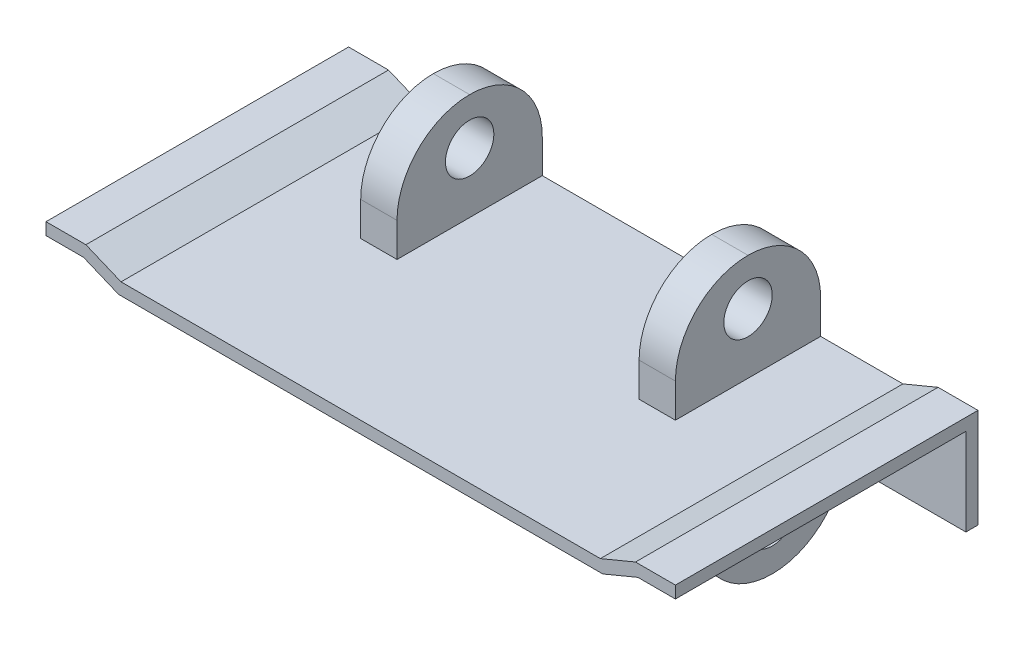
SolidWorks part; units mm, degrees
ref_plane "Front Plane" through (0, 0, 0) normal (0, 0, 1) x (1, 0, 0)
ref_plane "Top Plane" through (0, 0, 0) normal (0, 1, 0) x (1, 0, 0)
ref_plane "Right Plane" through (0, 0, 0) normal (1, 0, 0) x (0, 0, -1)
sketch "Sketch2" plane through (0, 0, 0) normal (0, 0, 1) x (1, 0, 0)
  line L0 (-5, 6) -> (-10, 6)
  line L1 (-5, 6) -> (5, 6) construction
  line L2 (-5, 6) -> (-5, -6) construction
  line L3 (-5, -6) -> (5, -6) construction
  line L4 (5, 6) -> (5, -6) construction
  line L5 (-5, 6) -> (5, -6) construction
  line L6 (-5, -6) -> (5, 6) construction
  line L7 (-10, 6) -> (-10, -6)
  line L8 (-10, -6) -> (-5, -6)
  line L9 (-5, -6) -> (-5, 6)
  line L10 (0, 6) -> (0, -6) construction
  line L11 (10, -6) -> (5, -6)
  line L12 (10, 6) -> (10, -6)
  line L13 (5, 6) -> (10, 6)
  line L14 (5, -6) -> (5, 6)
  point P0 (0, 0)
  point P11 (0, 0)
  point P16 (0, 6)
  dimension "D1" = 12
  dimension "D2" = 10
  dimension "D3" = 5
extrude "Boss-Extrude1" add sketch "Sketch2" along normal blind 12
sketch "Sketch4" plane through (0, 0, 0) normal (0, 0, 1) x (1, 0, 0)
  line L0 (0, 0) -> (0, 50000) construction
  line L1 (-6.1796, 6) -> (49993.8204, 6) construction
  line L2 (-10, 6) -> (-20, 6)
  line L3 (10, 6) -> (20, 6)
  line L4 (-20, 6) -> (-22.9016, 7.2064)
  line L5 (-22.9016, 7.2064) -> (-26, 7.2064)
  line L6 (-10, 7) -> (-19.8004, 7)
  line L7 (-19.8004, 7) -> (-22.702, 8.2064)
  line L8 (-22.702, 8.2064) -> (-26, 8.2064)
  line L9 (-26, 8.2064) -> (-26, 7.2064)
  line L10 (-10, 6) -> (10, 6)
  line L11 (-10, 7) -> (10, 7)
  line L12 (10, 7) -> (19.8004, 7)
  line L13 (19.8004, 7) -> (22.702, 8.2064)
  line L14 (20, 6) -> (22.9016, 7.2064)
  line L15 (22.9016, 7.2064) -> (26, 7.2064)
  line L16 (26, 8.2064) -> (26, 7.2064)
  line L17 (22.702, 8.2064) -> (26, 8.2064)
  point P19 (0, 6)
  point P20 (0, 7)
  dimension "D1" = 10
  dimension "D3" = 6
  dimension "D2" = 1
extrude "Boss-Extrude3" add sketch "Sketch4" along normal blind 25
sketch "Sketch9" plane through (0, 0, 12) normal (0, 0, 1) x (1, 0, 0)
  line L0 (-10, -6) -> (-5, -6) construction
  line L1 (-5, 6) -> (-7.5, 6)
  line L2 (-5, 6) -> (-5, -6)
  line L3 (-5, -6) -> (-7.5, -6)
  line L4 (-7.5, 6) -> (-7.5, -6)
  line L5 (0, 7.972) -> (0, -7.972) construction
  line L6 (5, -6) -> (7.5, -6)
  line L7 (7.5, 6) -> (7.5, -6)
  line L8 (5, 6) -> (7.5, 6)
  line L9 (5, 6) -> (5, -6)
  point P11 (0, 0)
  dimension "D1" = 2.5
extrude "Cut-Extrude1" [suppressed] cut sketch "Sketch9" against normal blind 10
sketch "Sketch5" plane through (0, 0, 0) normal (0, 0, 1) x (1, 0, 0)
  line L0 (-10, 4.6) -> (-10, 50004.6) construction
  line L1 (0, 0) -> (0, 50000) construction
  line L2 (-10, 7) -> (-10, 15.8)
  line L3 (19.8004, 7) -> (-19.8004, 7) construction
  line L4 (-10, 15.8) -> (-13, 15.8)
  line L5 (-13, 15.8) -> (-13, 7)
  line L6 (-13, 7) -> (-10, 7)
  line L7 (13, 7) -> (10, 7)
  line L8 (13, 15.8) -> (13, 7)
  line L9 (10, 15.8) -> (13, 15.8)
  line L10 (10, 7) -> (10, 15.8)
  dimension "D1" = 3
  dimension "D2" = 8.8
extrude "Boss-Extrude4" add sketch "Sketch5" along normal blind 12
sketch "Sketch7" plane through (0, 0, 0) normal (0, 0, 1) x (1, 0, 0)
  line L0 (-13, 5.6) -> (-13, -49994.4) construction
  line L1 (-19.8004, 5.6) -> (-19.8004, -49994.4) construction
  line L2 (-10.0004, -6) -> (49989.9996, -6) construction
  line L3 (-15.0004, 6) -> (-50015.0004, 6) construction
  line L4 (-15, 6) -> (-15, -6)
  line L5 (-15, -6) -> (-13, -6)
  line L6 (-13, -6) -> (-13, 6)
  line L7 (-13, 6) -> (-15, 6)
  line L8 (0, 0) -> (0, -50000) construction
  line L13 (0, -11.99) -> (0, 11.99) construction
  line L14 (13, -6) -> (13, 6)
  line L15 (15, -6) -> (13, -6)
  line L16 (15, 6) -> (15, -6)
  line L17 (13, 6) -> (15, 6)
  dimension "D1" = 2
extrude "Boss-Extrude5" add sketch "Sketch7" along normal blind 12
sketch "Sketch15" plane through (0, -6, 0) normal (0, -1, 0) x (1, 0, 0)
  line L16 (-10, 12) -> (-9.8, 12)
  line L17 (-10, 12) -> (-5, 12) construction
  line L18 (-10, 12) -> (-10, 0) construction
  line L19 (-9.8, 12) -> (-9.8, 0)
  line L20 (-10, 0) -> (-5, 0) construction
  line L21 (-9.8, 0) -> (-10, 0)
  line L22 (-10, 0) -> (-10, 12)
  line L23 (0, -11.99) -> (0, 11.99) construction
  line L24 (9.8, 0) -> (10, 0)
  line L25 (9.8, 12) -> (9.8, 0)
  line L26 (10, 12) -> (9.8, 12)
  line L27 (10, 0) -> (10, 12)
  line L28 (-13, 12) -> (-13.2, 12)
  line L29 (-15, 12) -> (-13, 12) construction
  line L30 (-13.2, 12) -> (-13.2, 0)
  line L31 (-15, 0) -> (-13, 0) construction
  line L32 (-13.2, 0) -> (-13, 0)
  line L33 (-13, 0) -> (-13, 12)
  line L34 (13.2, 0) -> (13, 0)
  line L35 (13.2, 12) -> (13.2, 0)
  line L36 (13, 12) -> (13.2, 12)
  line L37 (13, 0) -> (13, 12)
  dimension "D1" = 0.2
  dimension "D2" = 0.2
extrude "Cut-Extrude2" cut sketch "Sketch15" against normal up to surface (12 mm away) up to face at (0, 6, 7.3)
sketch "Sketch16" plane through (0, -6, 0) normal (0, -1, 0) x (1, 0, 0)
  line L0 (-5, 12) -> (-5.15, 12)
  line L1 (-9.8, 12) -> (-5, 12) construction
  line L2 (-5.15, 12) -> (-5.15, 0)
  line L3 (-9.8, 0) -> (-5, 0) construction
  line L4 (-5.15, 0) -> (-5, 0)
  line L5 (-5, 0) -> (-5, 12)
  line L6 (0, -11.99) -> (0, 11.99) construction
  line L7 (5.15, 0) -> (5, 0)
  line L8 (5.15, 12) -> (5.15, 0)
  line L9 (5, 12) -> (5.15, 12)
  line L10 (5, 0) -> (5, 12)
  dimension "D1" = 0.15
extrude "Cut-Extrude3" cut sketch "Sketch16" against normal up to surface (12 mm away) up to face at (0, 6, 7.3)
fillet "Fillet1" radius 6 8 edges at (7.475, -6, 0) (7.475, -6, 12) (-7.475, -6, 0) (-7.475, -6, 12) (-14.1, -6, 0) (-14.1, -6, 12) (14.1, -6, 0) (14.1, -6, 12)
hole_wizard "Ø4.0mm Dowel Hole2" positions "Sketch10" profile "Sketch11" hole size "Ø4.0" standard "ANSI Metric" end condition through all
sketch "Sketch10" plane through (15, 0, 0) normal (1, 0, 0) x (0, 0, -1)
  line L7 (-25, 6) -> (0, 6) construction
  line L9 (-12, 0) -> (-12, 6) construction
  point P0 (-6, -2)
  dimension "D1" = 6
  dimension "D2" = 8
sketch "Sketch11" plane through (15, -2, 6) normal (0, 1, 0) x (0, 0, -1)
  line L0 (0, 0) -> (0, 41)
  line L1 (0, 41) -> (2, 41)
  line L2 (2, 41) -> (2, 0)
  line L5 (2, 0) -> (0, 0)
  line L11 (0, -6.35) -> (0, 107.95) construction
  dimension "Thru Hole Dia." = 4
  dimension "Thru Hole Depth" = 41
fillet "Fillet2" radius 6 4 edges at (-11.5, 15.8, 0) (-11.5, 15.8, 12) (11.5, 15.8, 0) (11.5, 15.8, 12)
hole_wizard "Ø4.0mm Dowel Hole1" positions "Sketch12" profile "Sketch13" hole size "Ø4.0" standard "ANSI Metric"
sketch "Sketch12" plane through (13, 0, 0) normal (1, 0, 0) x (0, 0, -1)
  circle A0 centre (-6, -0.575) radius 2 construction
  circle A1 centre (-6, -0.575) radius 2 construction
  arc A7 (0, 9.8) -> (-6, 15.8) centre (-6, 9.8) ccw construction
  point P10 (-6, 11.975)
  dimension "D1" = 3.825
sketch "Sketch13" plane through (13, 11.975, 6) normal (0, 1, 0) x (0, 0, -1)
  line L0 (0, 0) -> (0, 27.2017)
  line L1 (0, 27.2017) -> (2, 26)
  line L2 (2, 26) -> (2, 0)
  line L5 (2, 0) -> (0, 0)
  line L10 (0, 27.2017) -> (-2, 26) construction
  line L11 (0, -6.35) -> (0, 107.95) construction
  dimension "Hole Dia." = 4
  dimension "Hole Depth" = 26
  dimension "Drill Angle" = 118
sketch "Sketch14" plane through (0, 0, 0) normal (0, 0, 1) x (1, 0, 0)
  line L4 (0, 14.6739) -> (0, -14.6739) construction
  line L5 (-26, 7.2064) -> (-22.9016, 7.2064)
  line L6 (-26, 6) -> (-26, 7.2064)
  line L7 (-20, 6) -> (-26, 6)
  line L8 (-22.9016, 7.2064) -> (-20, 6)
  line L13 (-15, 6) -> (-20, 6)
  line L14 (-26, 0) -> (-26, 6)
  line L15 (-15, 0) -> (-26, 0)
  line L18 (-15, 6) -> (-15, 0)
  line L21 (15, 6) -> (15, 0)
  line L22 (15, 0) -> (26, 0)
  line L23 (26, 0) -> (26, 6)
  line L24 (15, 6) -> (20, 6)
  line L25 (22.9016, 7.2064) -> (20, 6)
  line L26 (20, 6) -> (26, 6)
  line L27 (26, 6) -> (26, 7.2064)
  line L28 (26, 7.2064) -> (22.9016, 7.2064)
  point P11 (0, 0)
extrude "Boss-Extrude6" add sketch "Sketch14" along normal blind 1 contours L8 L5 L6 L7 | L14 L13 L7 | L27 L28 L25 L26 | L26 L24 L21 L22 L23 region at (-23.6483, 6.5391, 0) region at (-20.5, 3, 0) region at (20.5, 3, 0) region at (23.6483, 6.5391, 0)
sketch "Sketch18" plane through (-5.15, 0, 0) normal (1, 0, 0) x (0, 0, -1)
  line L1 (-2.9188, -0.6888) -> (-5.5949, 1.324)
  line L2 (-5.5949, 1.324) -> (-8.6762, 0.0128)
  line L3 (-8.6762, 0.0128) -> (-9.0812, -3.3112)
  line L4 (-9.0812, -3.3112) -> (-6.4051, -5.324)
  line L5 (-6.4051, -5.324) -> (-3.3238, -4.0128)
  line L6 (-3.3238, -4.0128) -> (-2.9188, -0.6888)
  circle A0 centre (-6, -2) radius 2.9 construction
  dimension "D1" = 5.8
extrude "Cut-Extrude4" cut sketch "Sketch18" against normal blind 2.4
mirror "Mirror1" about plane through (0, 0, 0) normal (1, 0, 0) of "Cut-Extrude4"
